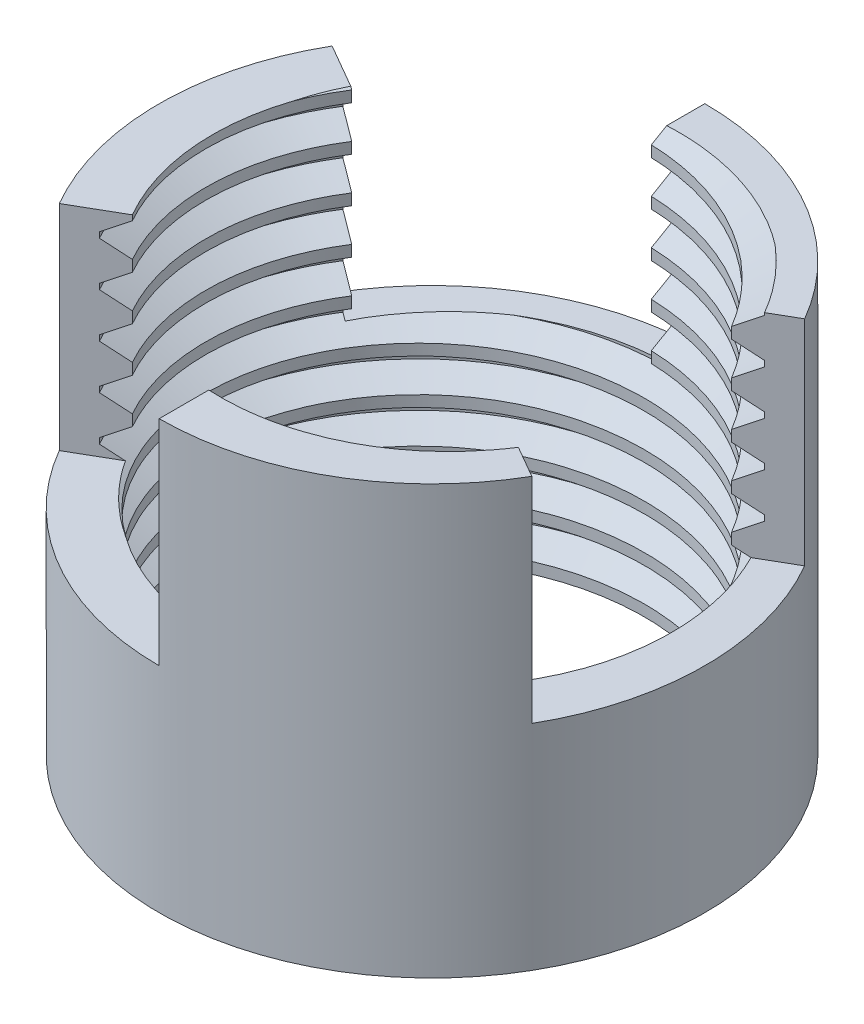
SolidWorks part; units mm, degrees
ref_plane "Front Plane" through (0, 0, 0) normal (0, 0, 1) x (1, 0, 0)
ref_plane "Top Plane" through (0, 0, 0) normal (0, 1, 0) x (1, 0, 0)
ref_plane "Right Plane" through (0, 0, 0) normal (1, 0, 0) x (0, 0, -1)
sketch "Sketch1" plane through (0, 0, 0) normal (1, 0, 0) x (0, 0, -1)
  line L0 (0, 0) -> (0, 12) construction
  line L1 (6.15, 0) -> (7.65, 0)
  line L2 (6.15, 0) -> (6.15, 12)
  line L3 (6.15, 12) -> (7.65, 12)
  line L4 (7.65, 0) -> (7.65, 12)
  point P7 (6.9, 12)
  dimension "D1" = 12
  dimension "D2" = 6.15
  dimension "D3" = 1.5
revolve "Revolve1" add sketch "Sketch1" angle 360 about L0
thread "Thread1" pitch 1.25 method cut profile "Thread Profile1" start angle 0, offset 1, length 14, pitch 1.25, diameter 12.3
ref_plane "Plane1" through (-6.15, 13, 0) normal (0, 0, 1) x (-1, 0, 0)
sketch "Thread Profile1" plane through (-6.15, 13, 0) normal (0, 0, 1) x (-1, 0, 0)
  line L0 (0, 0) -> (0, 1.25) construction
  line L1 (0, 0) -> (0.6766, 0.3906)
  line L2 (0.6766, 0.3906) -> (0.6766, 0.5469)
  line L3 (0.6766, 0.5469) -> (0, 0.9375)
  line L4 (0.6766, 0.4687) -> (0, 0.4687) construction
  line L11 (0, 0) -> (0, 0.9375)
  point P2 (0, 0)
  dimension "Pitch" = 1.25
  dimension "Profile_Angle" = 60
  dimension "Profile_Land" = 0.1562
  dimension "Profile_Height" = 0.6766
sketch "Sketch4" plane through (0, 12, 0) normal (0, 1, 0) x (1, 0, 0)
  line L0 (0, 7.65) -> (0, 0) construction
  line L1 (-6.6251, 3.825) -> (0, 0) construction
  line L2 (-6.6251, 3.825) -> (-5.3261, 3.075)
  line L3 (0, 7.65) -> (0, 6.15)
  arc A1 (0, 7.65) -> (-6.6251, 3.825) centre (0, 0) ccw
  circle A2 centre (0, 0) radius 7.65 construction
  arc A3 (0, 6.15) -> (-5.3261, 3.075) centre (0, 0) ccw
  circle A4 centre (0, 0) radius 6.15 construction
  dimension "D1" = 120
extrude "Cut-Extrude1" cut sketch "Sketch4" against normal blind 6
pattern_circular "CirPattern1" count 3 over 360 about axis through (0, 12, 0) along (0, -1, 0) of "Cut-Extrude1"
